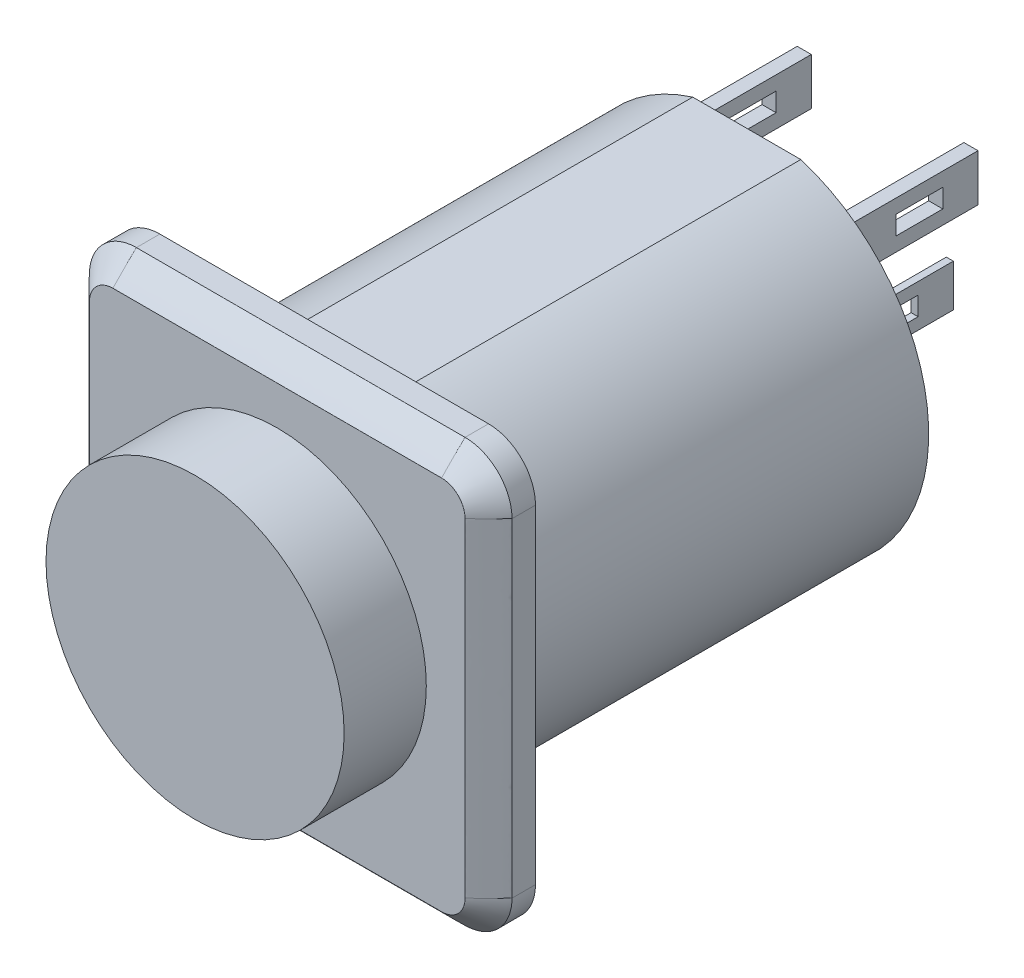
SolidWorks part; units mm, degrees
ref_plane "Front Plane" through (0, 0, 0) normal (0, 0, 1) x (1, 0, 0)
ref_plane "Top Plane" through (0, 0, 0) normal (0, 1, 0) x (1, 0, 0)
ref_plane "Right Plane" through (0, 0, 0) normal (1, 0, 0) x (0, 0, -1)
sketch "Sketch1" plane through (0, 0, 0) normal (0, 0, 1) x (1, 0, 0)
  line L1 (-9, 9) -> (9, 9)
  line L2 (-9, 9) -> (-9, -9)
  line L3 (-9, -9) -> (9, -9)
  line L4 (9, 9) -> (9, -9)
  line L5 (-9, 9) -> (9, -9) construction
  line L6 (-9, -9) -> (9, 9) construction
  point P0 (0, 0)
  dimension "D1" = 18
extrude "Boss-Extrude1" add sketch "Sketch1" along normal blind 2
fillet "Fillet1" radius 2 4 edges at (-9, -9, 1) (9, -9, 1) (-9, 9, 1) (9, 9, 1)
fillet "Fillet2" radius 1 8 edges at (-8.4142, 8.4142, 2) (0, 9, 2) (8.4142, 8.4142, 2) (9, 0, 2) (8.4142, -8.4142, 2) (0, -9, 2) (-8.4142, -8.4142, 2) (-9, 0, 2) conic radius 50
sketch "Sketch2" plane through (0, 0, 2) normal (0, 0, 1) x (1, 0, 0)
  circle A0 centre (0, 0) radius 6.35
  dimension "D1" = 12.7
extrude "Boss-Extrude2" add sketch "Sketch2" along normal blind 3.5 separate body
sketch "Sketch3" plane through (0, 0, 0) normal (0, 0, -1) x (-1, 0, 0)
  line L0 (-1000, 0) -> (49000, 0) construction
  line L1 (-2.3027, 7.4) -> (2.3027, 7.4)
  line L2 (-2.3027, -7.4) -> (2.3027, -7.4)
  circle A0 centre (0, 0) radius 7.75
  dimension "D1" = 15.5
  dimension "D2" = 14.8
extrude "Boss-Extrude3" add sketch "Sketch3" along normal blind 18 contours A0 L0 L1 | L0 A0 L2 region at (0, 3.24, 0) region at (0, -3.24, 0)
sketch "Sketch4" plane through (0, 0, -18) normal (0, 0, -1) x (-1, 0, 0)
  line L0 (0, -1000) -> (0, 49000) construction
  line L1 (-1000, 0) -> (49000, 0) construction
  line L2 (-3.85, 5.5) -> (-3.25, 5.5)
  line L3 (-3.85, 5.5) -> (-3.85, 3.5)
  line L4 (-3.85, 3.5) -> (-3.25, 3.5)
  line L5 (-3.25, 5.5) -> (-3.25, 3.5)
  line L6 (-3.85, 5.5) -> (-3.25, 3.5) construction
  line L7 (-3.85, 3.5) -> (-3.25, 5.5) construction
  line L8 (-2.8, 0.9) -> (-2.5, 0.9)
  line L9 (-2.8, 0.9) -> (-2.8, -0.9)
  line L10 (-2.8, -0.9) -> (-2.5, -0.9)
  line L11 (-2.5, 0.9) -> (-2.5, -0.9)
  line L12 (-2.8, 0.9) -> (-2.5, -0.9) construction
  line L13 (-2.8, -0.9) -> (-2.5, 0.9) construction
  line L14 (2.8, -0.9) -> (2.5, -0.9)
  line L15 (2.5, 0.9) -> (2.5, -0.9)
  line L16 (2.8, 0.9) -> (2.5, 0.9)
  line L17 (2.8, 0.9) -> (2.8, -0.9)
  line L18 (3.85, 3.5) -> (3.25, 3.5)
  line L19 (3.25, 5.5) -> (3.25, 3.5)
  line L20 (3.85, 5.5) -> (3.25, 5.5)
  line L21 (3.85, 5.5) -> (3.85, 3.5)
  point P1 (-3.55, 4.5)
  point P8 (-2.65, 0)
  point P14 (0, 0)
  dimension "D1" = 0.3
  dimension "D2" = 0.6
  dimension "D3" = 2
  dimension "D4" = 1.8
  dimension "D5" = 5
  dimension "D6" = 6.5
  dimension "D7" = 4.5
extrude "Boss-Extrude4" add sketch "Sketch4" along normal blind 6 separate body
sketch "Sketch5" plane through (3.85, 0, 0) normal (1, 0, 0) x (0, 0, -1)
  line L0 (24, 5.5) -> (24, 3.5) construction
  line L1 (20.5, 4.9) -> (22.5, 4.9)
  line L2 (20.5, 4.9) -> (20.5, 4.1)
  line L3 (20.5, 4.1) -> (22.5, 4.1)
  line L4 (22.5, 4.9) -> (22.5, 4.1)
  line L5 (20.5, 4.9) -> (22.5, 4.1) construction
  line L6 (20.5, 4.1) -> (22.5, 4.9) construction
  line L7 (20.5, 0.4) -> (22.5, 0.4)
  line L8 (20.5, 0.4) -> (20.5, -0.4)
  line L9 (20.5, -0.4) -> (22.5, -0.4)
  line L10 (22.5, 0.4) -> (22.5, -0.4)
  line L11 (20.5, 0.4) -> (22.5, -0.4) construction
  line L12 (20.5, -0.4) -> (22.5, 0.4) construction
  line L13 (24, 0.9) -> (24, -0.9) construction
  point P0 (21.5, 4.5)
  point P5 (21.5, 0)
  point P10 (0, 0)
  point P13 (24, 4.5)
  point P14 (0, 0)
  point P17 (24, 0)
  dimension "D1" = 1.5
  dimension "D2" = 1.5
  dimension "D3" = 2
  dimension "D4" = 0.8
extrude "Cut-Extrude1" cut sketch "Sketch5" against normal through all
